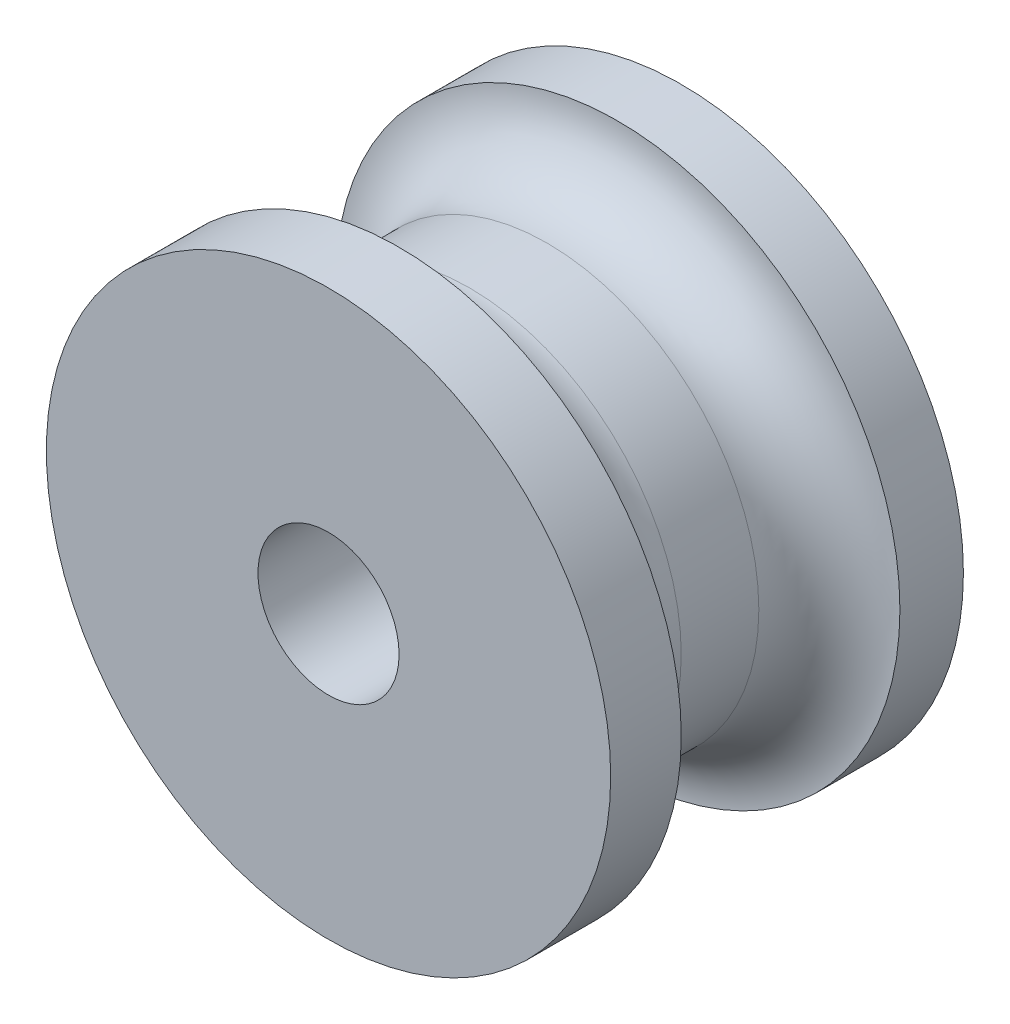
SolidWorks part; units mm, degrees
ref_plane "前视基准面" through (0, 0, 0) normal (0, 0, 1) x (1, 0, 0)
ref_plane "上视基准面" through (0, 0, 0) normal (0, 1, 0) x (1, 0, 0)
ref_plane "右视基准面" through (0, 0, 0) normal (1, 0, 0) x (0, 0, -1)
sketch "草图1" plane through (0, 0, 0) normal (0, 0, 1) x (1, 0, 0)
  circle A0 centre (0, 0) radius 40
  dimension "D1" = 80
extrude "凸台-拉伸1" add sketch "草图1" along normal blind 50
ref_plane "基准面1" through (0, 0, 25) normal (0, 0, 1) x (1, 0, 0)
sketch "草图2" plane through (0, 0, 25) normal (0, 0, 1) x (1, 0, 0)
  circle A0 centre (0, 0) radius 30
  dimension "D1" = 60
extrude "切除-拉伸1" cut sketch "草图2" along normal blind 15 and the other way blind 16 from offset 0 flip side to cut contours A0
fillet "圆角1" radius 10 1 edges at (30, 0, 40) type face fillet first side face at (30, 0, 40) second side face at (30, 0, 9)
fillet "圆角2" radius 10 1 edges at (30, 0, 9) type face fillet first side face at (30, 0, 9) second side face at (30, 0, 30)
sketch "草图3" plane through (0, 0, 25) normal (0, 0, 1) x (1, 0, 0)
  circle A0 centre (0, 0) radius 10
  dimension "D1" = 20
extrude "切除-拉伸2" cut sketch "草图3" against normal through all both and the other way through all from offset 0 contours A0
